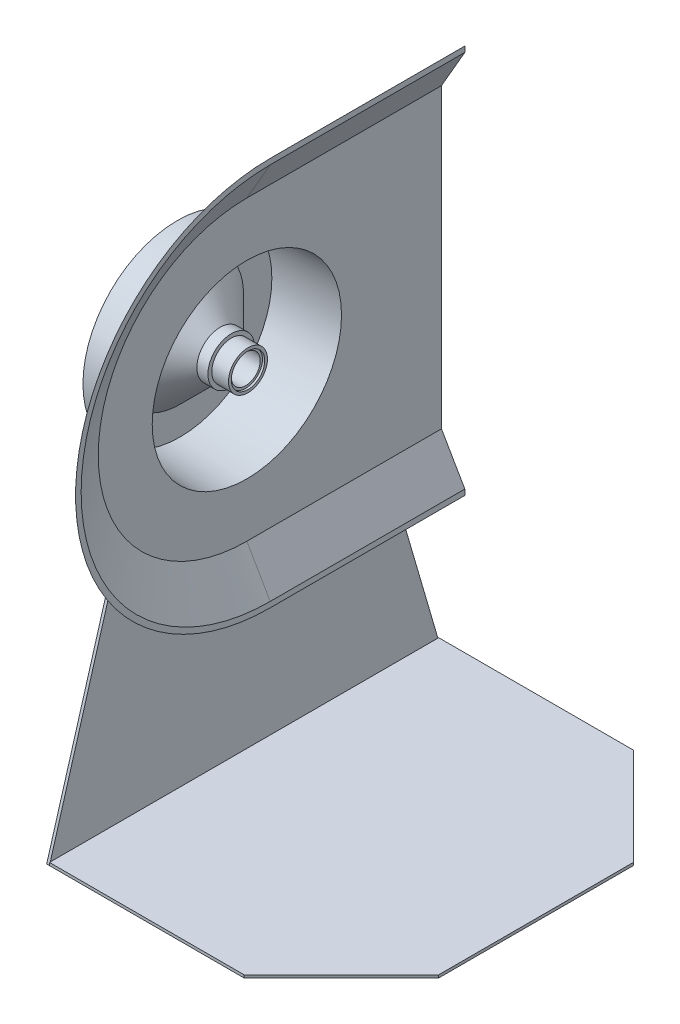
SolidWorks part; units mm, degrees
ref_plane "Plan de face" through (0, 0, 0) normal (0, 0, 1) x (1, 0, 0)
ref_plane "Plan de dessus" through (0, 0, 0) normal (0, 1, 0) x (1, 0, 0)
ref_plane "Plan de droite" through (0, 0, 0) normal (1, 0, 0) x (0, 0, -1)
sketch "Esquisse2" plane through (0, 0, 0) normal (0, 0, 1) x (1, 0, 0)
  line L0 (0, 350) -> (0, 0)
  line L5 (-47, 268.5936) -> (0, 350)
  line L6 (-47, 268.5936) -> (-47, 0)
  line L7 (-47, 0) -> (0, 0)
  dimension "D1" = 150
  dimension "D2" = 350
  dimension "D3" = 47
revolve "Revolve1" add sketch "Esquisse2" angle 180 about L7
sketch "Sketch12" plane through (-47, 0, 0) normal (-1, 0, 0) x (0, 0, 1)
  circle A0 centre (0, 0) radius 175
extrude "Boss-Extrude2" add sketch "Sketch12" along normal blind 120 draft 2.5
sketch "Sketch13" plane through (0, 0, 0) normal (0, 0, -1) x (-1, 0, 0)
  line L0 (0, 350) -> (47, 268.5936)
  line L1 (47, 268.5936) -> (47, -268.5936)
  line L2 (47, -268.5936) -> (0, -350)
  line L3 (0, -350) -> (0, 350)
extrude "Boss-Extrude3" add sketch "Sketch13" along normal blind 350
sketch "Sketch14" plane through (-167, 0, 0) normal (-1, 0, 0) x (0, 0, 1)
  circle A0 centre (0, 0) radius 112
extrude "Cut-Extrude1" cut sketch "Sketch14" against normal blind 32 draft 45 contours A0
sketch "Sketch17" plane through (-135, 0, 0) normal (-1, 0, 0) x (0, 0, 1)
  circle A0 centre (0, 0) radius 31
extrude "Cut-Extrude3" cut sketch "Sketch17" against normal blind 6
shell "Shell1" thickness 5 removed face at (-23.5, 0, -350) removed face at (0, 0, -87.5)
sketch "Sketch18" plane through (0, 0, 0) normal (0, 0, 1) x (1, 0, 0)
  line L0 (-130, 82.0711) -> (-89.9289, 42)
  line L1 (-89.9289, 42) -> (-70, 42)
  line L2 (-70, 42) -> (-70, 35.0493)
  line L3 (-70, 35.0493) -> (-40, 35.0493)
  line L4 (-40, 35.0493) -> (-40, 30.0944)
  line L5 (-40, 30.0944) -> (-44, 30.0944)
  line L6 (-44, 30.0944) -> (-44, 26)
  line L7 (-44, 26) -> (-124, 26)
  line L8 (-124, -36) -> (-124, 36) construction
  line L9 (-124, 26) -> (-124, 36)
  line L10 (-124, 36) -> (-130, 36)
  line L11 (-130, 36) -> (-130, 82.0711)
  line L13 (0, 0) -> (-213.9916, 0) construction
  line L14 (-130, 82.0711) -> (-162, 114.0711) construction
  dimension "D1" = 26
  dimension "D2" = 26
  dimension "D3" = 80
  dimension "D4" = 4
  dimension "D5" = 42
sketch "Sketch15" plane through (-135, 0, 0) normal (-1, 0, 0) x (0, 0, 1)
  circle A0 centre (0, 0) radius 26
extrude "Cut-Extrude2" cut sketch "Sketch15" against normal through all
revolve "Revolve2" add sketch "Sketch18" angle 360 about L13
sketch "Sketch19" plane through (0, 0, 0) normal (0, 0, 1) x (1, 0, 0)
  line L0 (0, 0) -> (-197.0961, 0) construction
  line L1 (0, -350) -> (0, 350) construction
sketch "Sketch20" plane through (-47, 0, 0) normal (-1, 0, 0) x (0, 0, 1)
  line L1 (-350, -600) -> (350, -600)
  line L3 (175, 0) -> (350, -600)
  line L4 (-175, 0) -> (-350, -600)
  arc A0 (-175, 0) -> (175, 0) centre (0, 0) ccw
  circle A1 centre (0, 0) radius 175 construction
  point P6 (0, -600)
  dimension "D1" = 600
  dimension "D2" = 700
  dimension "D3" = 0
  dimension "D4" = 0
  dimension "D5" = 350
extrude "Boss-Extrude4" add sketch "Sketch20" along normal blind 5 contours L3 L1 L4 A0
sketch "Sketch21" plane through (0, -600, 0) normal (0, -1, 0) x (1, 0, 0)
  line L2 (-47, 350) -> (-47, -350)
  line L5 (-47, 350) -> (303, 350)
  line L6 (303, 350) -> (478, 175)
  line L7 (478, 175) -> (478, -175)
  line L8 (478, -175) -> (303, -350)
  line L9 (303, -350) -> (-47, -350)
  line L10 (478, 0) -> (0, 0) construction
  dimension "D1" = 700
  dimension "D2" = 135
  dimension "D3" = 135
  dimension "D4" = 350
  dimension "D5" = 350
  dimension "D6" = 350
  dimension "D7" = 90
extrude "Boss-Extrude5" add sketch "Sketch21" against normal blind 5 contours L5 L6 L7 L8 L9 L2
sketch "Esquisse3" plane through (-129, 0, 0) normal (-1, 0, 0) x (0, 0, 1)
  line L1 (-4, 30) -> (4, 30)
  line L2 (-4, 30) -> (-4, 26)
  line L4 (4, 30) -> (4, 26)
  line L6 (4, 26) -> (4, 25)
  line L7 (4, 25) -> (-4, 25)
  line L8 (-4, 26) -> (-4, 25)
  point P4 (0, 30)
  dimension "D2" = 4
  dimension "D3" = 8
  dimension "D4" = 0
  dimension "D1" = 26
  dimension "D5" = 1
  dimension "D6" = 1
extrude "Enlèv. mat.-Extru.2" cut sketch "Esquisse3" against normal up to next contours L2 L8 L7 L6 L4 L1
equation "\"D4@Esquisse3\"=0"
